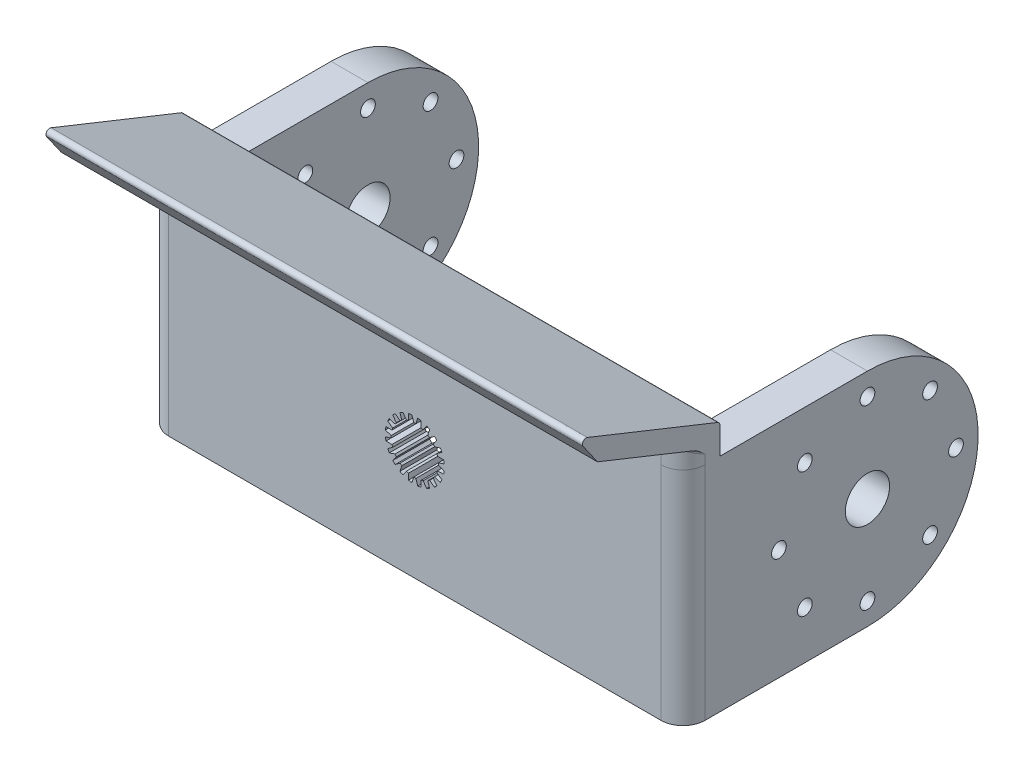
SolidWorks part; units mm, degrees
ref_plane "Front Plane" through (0, 0, 0) normal (0, 0, 1) x (1, 0, 0)
ref_plane "Top Plane" through (0, 0, 0) normal (0, 1, 0) x (1, 0, 0)
ref_plane "Right Plane" through (0, 0, 0) normal (1, 0, 0) x (0, 0, -1)
sketch "Sketch1" plane through (0, 0, 0) normal (0, 0, 1) x (1, 0, 0)
  line L0 (36.35, -15) -> (36.35, 15)
  line L1 (-36.35, -15) -> (-36.35, 15)
  line L2 (0, 0) -> (-36.35, 0)
  line L3 (0, 0) -> (36.35, 0)
  line L4 (-36.35, 15) -> (36.35, 15)
  line L5 (-36.35, -15) -> (36.35, -15)
  circle A0 centre (0, 0) radius 5
  point P10 (-36.35, 0)
  point P11 (36.35, 0)
  dimension "D1" = 10
  dimension "D2" = 30
  dimension "D4" = 36.35
  dimension "D5" = 36.35
extrude "Boss-Extrude1" add sketch "Sketch1" along normal blind 5 contours A0 L3 L0 L4 L1 L2 | L3 A0 L2 | L2 A0 L3 | A0 L2 L1 L5 L0 L3
sketch "Sketch4" plane through (0, 0, 0) normal (0, 0, -1) x (-1, 0, 0)
  line L0 (36.35, 15) -> (-36.35, 15) construction
  line L1 (-36.35, -15) -> (-31.35, -15)
  line L2 (-36.35, -15) -> (-36.35, 15)
  line L3 (-36.35, 15) -> (-31.35, 15)
  line L4 (-31.35, -15) -> (-31.35, 15)
  dimension "D1" = 5
extrude "Boss-Extrude4" add sketch "Sketch4" along normal blind 35
sketch "Sketch5" plane through (36.35, 0, 0) normal (1, 0, 0) x (0, 0, -1)
  line L0 (35, 0) -> (20, 0)
  line L1 (35, 15) -> (35, -15) construction
  circle A0 centre (20, 0) radius 15
  circle A1 centre (20, 0) radius 3
  dimension "D2" = 6
  dimension "D1" = 15
extrude "Cut-Extrude2" cut sketch "Sketch5" against normal blind 40
sketch "Sketch6" plane through (31.35, 0, 0) normal (-1, 0, 0) x (0, 0, 1)
  line L0 (-35, 15) -> (0, 15) construction
  line L1 (-35, -15) -> (0, -15) construction
  line L2 (-20, 15) -> (-35, 15)
  line L3 (-35, 15) -> (-35, -15)
  line L4 (-35, -15) -> (-20, -15)
  arc A0 (-20, 15) -> (-20, -15) centre (-20, 0) ccw
  circle A1 centre (-20, 0) radius 15 construction
  line M7 (0, 15) -> (-35, 15)
  line M8 (-35, 15) -> (-35, -15)
  line M9 (-35, -15) -> (0, -15)
extrude "Cut-Extrude3" cut sketch "Sketch6" against normal blind 10 contours A0 M7 M8 | A0 L3 M9
sketch "Sketch7" plane through (31.35, 0, 0) normal (-1, 0, 0) x (0, 0, 1)
  circle A0 centre (-28.4853, 8.4853) radius 1
  circle A1 centre (-11.5147, 8.4853) radius 1
  circle A2 centre (-8, 0) radius 1
  circle A3 centre (-32, 0) radius 1
  circle A4 centre (-11.5147, -8.4853) radius 1
  circle A6 centre (-20, 12) radius 1
  circle A7 centre (-28.4853, -8.4853) radius 1
  circle A8 centre (-20, -12) radius 1
extrude "Cut-Extrude4" cut sketch "Sketch7" against normal blind 10
fillet "Fillet2" radius 3 1 edges at (36.35, 0, 5)
fillet "Fillet3" radius 3 1 edges at (31.35, 0, 0)
sketch "Sketch8" plane through (-36.35, 0, 0) normal (-1, 0, 0) x (0, 0, 1)
  line L0 (0, 15) -> (0, 19)
  line L1 (0, 19) -> (20.4796, 27.1918)
  line L2 (20.4796, 27.1918) -> (20.4796, 24.1918)
  line L3 (20.4796, 24.1918) -> (5, 18)
  line L4 (5, 18) -> (5, 15)
  line L6 (0, 15) -> (5, 15)
  dimension "D1" = 4
  dimension "D2" = 3
  dimension "D3" = 3
extrude "Boss-Extrude5" add sketch "Sketch8" against normal up to surface (72.7 mm away) up to face at (36.35, -9.4853, -11.5147)
fillet "Fillet4" radius 3 1 edges at (36.35, 16.5, 5)
mirror "Mirror2" about plane through (0, 0, 0) normal (1, 0, 0) of "Cut-Extrude3", "Cut-Extrude2", "Boss-Extrude4", "Cut-Extrude4"
fillet "Fillet5" radius 3 1 edges at (-36.35, 1.5, 5)
fillet "Fillet6" radius 3 1 edges at (-31.35, 0, 0)
chamfer "Chamfer1" distance 4 angle 35 1 edges at (0, 24.1918, 20.4796)
sketch "Sketch9" plane through (0, 0, 5) normal (0, 0, 1) x (1, 0, 0)
  line L0 (3.9776, 0.4069) -> (3.1976, 0.1569)
  line L1 (3.1976, 0.1569) -> (3.1976, -0.1431)
  line L2 (3.1976, -0.1431) -> (3.9776, -0.3931)
  line L3 (3.1976, 0.0069) -> (-0.0024, 0.0069) construction
  line L4 (3.9064, -0.8426) -> (3.0874, -0.8393)
  line L5 (3.0874, -0.8393) -> (2.9947, -1.1246)
  line L6 (2.9947, -1.1246) -> (3.6592, -1.6034)
  line L7 (3.4526, -2.0089) -> (2.6747, -1.7527)
  line L8 (2.6747, -1.7527) -> (2.4983, -1.9954)
  line L9 (2.4983, -1.9954) -> (2.9824, -2.6561)
  line L10 (2.6606, -2.9778) -> (1.9999, -2.4938)
  line L11 (1.9999, -2.4938) -> (1.7572, -2.6701)
  line L12 (1.7572, -2.6701) -> (2.0134, -3.4481)
  line L13 (1.6079, -3.6547) -> (1.1292, -2.9901)
  line L14 (1.1292, -2.9901) -> (0.8438, -3.0828)
  line L15 (0.8438, -3.0828) -> (0.8471, -3.9019)
  line L16 (0.3976, -3.9731) -> (0.1476, -3.1931)
  line L17 (0.1476, -3.1931) -> (-0.1524, -3.1931)
  line L18 (-0.1524, -3.1931) -> (-0.4024, -3.9731)
  line L19 (-0.8518, -3.9019) -> (-0.8485, -3.0828)
  line L20 (-0.8485, -3.0828) -> (-1.1339, -2.9901)
  line L21 (-1.1339, -2.9901) -> (-1.6126, -3.6547)
  line L22 (-2.0181, -3.4481) -> (-1.7619, -2.6701)
  line L23 (-1.7619, -2.6701) -> (-2.0046, -2.4938)
  line L24 (-2.0046, -2.4938) -> (-2.6653, -2.9778)
  line L25 (-2.9871, -2.6561) -> (-2.503, -1.9954)
  line L26 (-2.503, -1.9954) -> (-2.6794, -1.7527)
  line L27 (-2.6794, -1.7527) -> (-3.4573, -2.0089)
  line L28 (-3.6639, -1.6034) -> (-2.9994, -1.1246)
  line L29 (-2.9994, -1.1246) -> (-3.0921, -0.8393)
  line L30 (-3.0921, -0.8393) -> (-3.9111, -0.8426)
  line L31 (-3.9823, -0.3931) -> (-3.2024, -0.1431)
  line L32 (-3.2024, -0.1431) -> (-3.2024, 0.1569)
  line L33 (-3.2024, 0.1569) -> (-3.9823, 0.4069)
  line L34 (-3.9111, 0.8563) -> (-3.0921, 0.8531)
  line L35 (-3.0921, 0.8531) -> (-2.9994, 1.1384)
  line L36 (-2.9994, 1.1384) -> (-3.6639, 1.6172)
  line L37 (-3.4573, 2.0226) -> (-2.6794, 1.7664)
  line L38 (-2.6794, 1.7664) -> (-2.503, 2.0092)
  line L39 (-2.503, 2.0092) -> (-2.9871, 2.6699)
  line L40 (-2.6653, 2.9916) -> (-2.0046, 2.5076)
  line L41 (-2.0046, 2.5076) -> (-1.7619, 2.6839)
  line L42 (-1.7619, 2.6839) -> (-2.0181, 3.4619)
  line L43 (-1.6126, 3.6684) -> (-1.1339, 3.0039)
  line L44 (-1.1339, 3.0039) -> (-0.8485, 3.0966)
  line L45 (-0.8485, 3.0966) -> (-0.8518, 3.9157)
  line L46 (-0.4024, 3.9868) -> (-0.1524, 3.2069)
  line L47 (-0.1524, 3.2069) -> (0.1476, 3.2069)
  line L48 (0.1476, 3.2069) -> (0.3976, 3.9868)
  line L49 (0.8471, 3.9157) -> (0.8438, 3.0966)
  line L50 (0.8438, 3.0966) -> (1.1292, 3.0039)
  line L51 (1.1292, 3.0039) -> (1.6079, 3.6684)
  line L52 (2.0134, 3.4619) -> (1.7572, 2.6839)
  line L53 (1.7572, 2.6839) -> (1.9999, 2.5076)
  line L54 (1.9999, 2.5076) -> (2.6606, 2.9916)
  line L55 (2.9824, 2.6699) -> (2.4983, 2.0092)
  line L56 (2.4983, 2.0092) -> (2.6747, 1.7664)
  line L57 (2.6747, 1.7664) -> (3.4526, 2.0226)
  line L58 (3.6592, 1.6172) -> (2.9947, 1.1384)
  line L59 (2.9947, 1.1384) -> (3.0874, 0.8531)
  line L60 (3.0874, 0.8531) -> (3.9064, 0.8563)
  arc A0 (-2.6653, 2.9916) -> (-2.9871, 2.6699) centre (-0.0024, 0.0069) ccw
  arc A1 (-3.4573, 2.0226) -> (-3.6639, 1.6172) centre (-0.0024, 0.0069) ccw
  arc A2 (-3.9111, 0.8563) -> (-3.9823, 0.4069) centre (-0.0024, 0.0069) ccw
  arc A3 (-3.9823, -0.3931) -> (-3.9111, -0.8426) centre (-0.0024, 0.0069) ccw
  arc A4 (-3.6639, -1.6034) -> (-3.4573, -2.0089) centre (-0.0024, 0.0069) ccw
  arc A5 (-2.9871, -2.6561) -> (-2.6653, -2.9778) centre (-0.0024, 0.0069) ccw
  arc A6 (-2.0181, -3.4481) -> (-1.6126, -3.6547) centre (-0.0024, 0.0069) ccw
  arc A7 (-0.8518, -3.9019) -> (-0.4024, -3.9731) centre (-0.0024, 0.0069) ccw
  arc A8 (0.3976, -3.9731) -> (0.8471, -3.9019) centre (-0.0024, 0.0069) ccw
  arc A9 (1.6079, -3.6547) -> (2.0134, -3.4481) centre (-0.0024, 0.0069) ccw
  arc A10 (2.6606, -2.9778) -> (2.9824, -2.6561) centre (-0.0024, 0.0069) ccw
  arc A11 (3.4526, -2.0089) -> (3.6592, -1.6034) centre (-0.0024, 0.0069) ccw
  arc A12 (3.9064, -0.8426) -> (3.9776, -0.3931) centre (-0.0024, 0.0069) ccw
  arc A13 (3.9776, 0.4069) -> (3.9064, 0.8563) centre (-0.0024, 0.0069) ccw
  arc A14 (3.6592, 1.6172) -> (3.4526, 2.0226) centre (-0.0024, 0.0069) ccw
  arc A15 (2.9824, 2.6699) -> (2.6606, 2.9916) centre (-0.0024, 0.0069) ccw
  arc A16 (2.0134, 3.4619) -> (1.6079, 3.6684) centre (-0.0024, 0.0069) ccw
  arc A17 (0.8471, 3.9157) -> (0.3976, 3.9868) centre (-0.0024, 0.0069) ccw
  arc A18 (-0.4024, 3.9868) -> (-0.8518, 3.9157) centre (-0.0024, 0.0069) ccw
  arc A19 (-1.6126, 3.6684) -> (-2.0181, 3.4619) centre (-0.0024, 0.0069) ccw
  point P82 (-0.1581, 1.199)
  dimension "D1" = 0.3
  dimension "D2" = 0.8
  dimension "D3" = 3.2
extrude "Cut-Extrude5" cut sketch "Sketch9" against normal blind 5
fillet "Fillet8" radius 0.5 1 edges at (0, 26.8028, 19.507)
fillet "Fillet9" radius 0.5 1 edges at (0, 19, 0)
fillet "Fillet10" radius 0.5 3 edges at (35.4713, 17.6485, 4.1213) (-35.4713, 17.6485, 4.1213) (0, 18, 5)
equation "\"mm\"=35"
